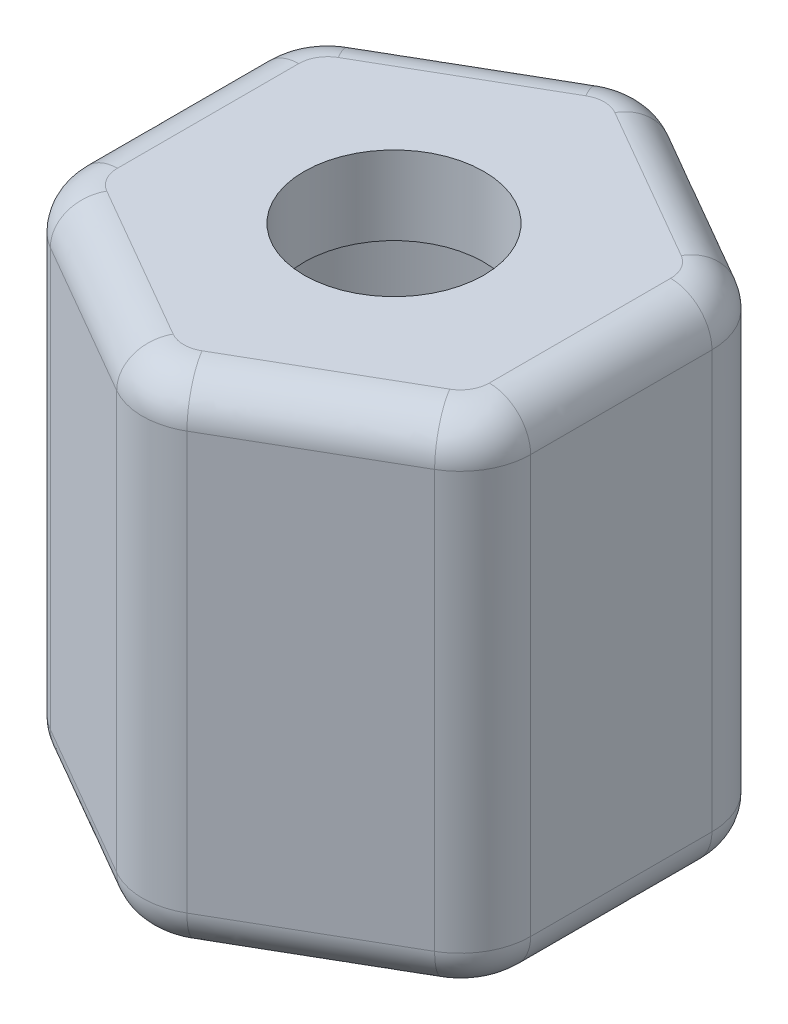
SolidWorks part; units mm, degrees
ref_plane "Front Plane" through (0, 0, 0) normal (0, 0, 1) x (1, 0, 0)
ref_plane "Top Plane" through (0, 0, 0) normal (0, 1, 0) x (1, 0, 0)
ref_plane "Right Plane" through (0, 0, 0) normal (1, 0, 0) x (0, 0, -1)
sketch "Sketch1" plane through (0, 0, 0) normal (0, 1, 0) x (1, 0, 0)
  line L1 (0, 12.7017) -> (-11, 6.3509)
  line L2 (-11, 6.3509) -> (-11, -6.3509)
  line L3 (-11, -6.3509) -> (0, -12.7017)
  line L4 (0, -12.7017) -> (11, -6.3509)
  line L5 (11, -6.3509) -> (11, 6.3509)
  line L6 (11, 6.3509) -> (0, 12.7017)
  circle A0 centre (0, 0) radius 11 construction
extrude "Boss-Extrude1" add sketch "Sketch1" along normal blind 24.2
sketch "Sketch3" plane through (0, 24.2, 0) normal (0, 1, 0) x (1, 0, 0)
  circle A0 centre (0, 0) radius 8.85
  dimension "D1" = 17.7
extrude "Cut-Extrude1" cut sketch "Sketch3" against normal blind 24.2
sketch "Sketch4" plane through (0, 24.2, 0) normal (0, 1, 0) x (1, 0, 0)
  line L0 (-11, 6.3509) -> (-11, -6.3509) construction
  line L1 (-11, -6.3509) -> (0, -12.7017) construction
  line L2 (0, -12.7017) -> (11, -6.3509) construction
  line L3 (11, -6.3509) -> (11, 6.3509) construction
  line L4 (11, 6.3509) -> (0, 12.7017) construction
  line L5 (0, 12.7017) -> (-11, 6.3509) construction
  line L6 (-11, 6.3509) -> (-11, -6.3509)
  line L7 (-11, -6.3509) -> (0, -12.7017)
  line L8 (0, -12.7017) -> (11, -6.3509)
  line L9 (11, -6.3509) -> (11, 6.3509)
  line L10 (11, 6.3509) -> (0, 12.7017)
  line L11 (0, 12.7017) -> (-11, 6.3509)
  circle A0 centre (0, 0) radius 4.35
  dimension "D1" = 8.7
extrude "Boss-Extrude2" add sketch "Sketch4" against normal blind 3.8
fillet "Fillet1" radius 3.4 6 edges at (-11, 12.1, -6.3509) (-11, 12.1, 6.3509) (0, 12.1, 12.7017) (11, 12.1, 6.3509) (11, 12.1, -6.3509) (0, 12.1, -12.7017)
fillet "Fillet2" radius 2 12 edges at (-10.5445, 0, -6.0879) (-11, 0, 0) (-10.5445, 0, 6.0879) (-5.5, 0, 9.5263) (0, 0, 12.1757) (5.5, 0, 9.5263) (10.5445, 0, 6.0879) (11, 0, 0) (10.5445, 0, -6.0879) (5.5, 0, -9.5263) (0, 0, -12.1757) (-5.5, 0, -9.5263) tangent propagation no first distance on face at (0, 0, 8.85)
fillet "Fillet4" radius 2 12 edges at (-10.5445, 24.2, -6.0879) (-11, 24.2, 0) (-10.5445, 24.2, 6.0879) (-5.5, 24.2, 9.5263) (0, 24.2, 12.1757) (5.5, 24.2, 9.5263) (10.5445, 24.2, 6.0879) (11, 24.2, 0) (10.5445, 24.2, -6.0879) (5.5, 24.2, -9.5263) (0, 24.2, -12.1757) (-5.5, 24.2, -9.5263) first distance on face at (-10.0361, 13.1, -6.2851) first distance on face at (-11, 13.1, -1.097) first distance on face at (-10.4611, 13.1, 5.549) first distance on face at (-6.45, 13.1, 8.9778) first distance on face at (-0.425, 13.1, 11.8341) first distance on face at (4.55, 13.1, 10.0748) first distance on face at (10.0361, 13.1, 6.2851) first distance on face at (11, 13.1, 1.097) first distance on face at (10.4611, 13.1, -5.549) first distance on face at (6.45, 13.1, -8.9778) first distance on face at (0.425, 13.1, -11.8341) first distance on face at (-4.55, 13.1, -10.0748)
